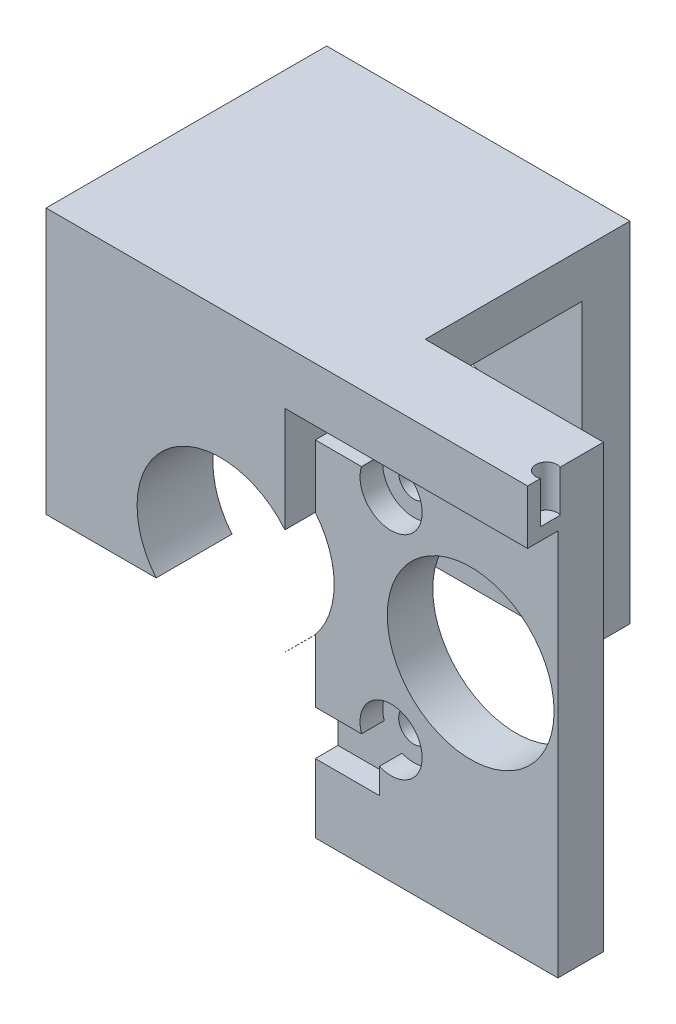
SolidWorks part; units mm, degrees
material "ABS"
ref_plane "Front Plane" through (0, 0, 0) normal (0, 0, 1) x (1, 0, 0)
ref_plane "Top Plane" through (0, 0, 0) normal (0, 1, 0) x (1, 0, 0)
ref_plane "Right Plane" through (0, 0, 0) normal (1, 0, 0) x (0, 0, -1)
sketch "Sketch1" plane through (0, 0, 0) normal (0, 0, 1) x (1, 0, 0)
  line L1 (-76.1871, 64.9281) -> (16.8129, 64.9281)
  line L2 (-76.1871, 64.9281) -> (-76.1871, -35.0719)
  line L3 (-76.1871, -35.0719) -> (16.8129, -35.0719)
  line L4 (16.8129, 64.9281) -> (16.8129, -35.0719)
  dimension "D1" = 93
  dimension "D2" = 100
extrude "Boss-Extrude2" add sketch "Sketch1" along normal blind 10 contours L1 L4 L3 L2
sketch "Sketch3" plane through (0, 0, 0) normal (0, 0, -1) x (-1, 0, 0)
  line L0 (76.1871, -35.0719) -> (-16.8129, -35.0719) construction
  line L1 (-16.8129, 64.9281) -> (-6.8129, 64.9281)
  line L2 (-16.8129, 64.9281) -> (-16.8129, -35.0719)
  line L3 (-16.8129, -35.0719) -> (-6.8129, -35.0719)
  line L4 (-6.8129, 64.9281) -> (-6.8129, -35.0719)
  line L5 (-16.8129, 64.9281) -> (-16.8129, -35.0719) construction
  dimension "D1" = 0
  dimension "D2" = 0
  dimension "D3" = 10
  dimension "D4" = 100
sketch "Sketch4" plane through (16.8129, 0, 0) normal (1, 0, 0) x (0, 0, -1)
  line L0 (-10, 64.9281) -> (-10, -35.0719) construction
  line L1 (-10, -5.0719) -> (0.01, -5.0719)
  line L2 (-10, -5.0719) -> (-10, -20.0719)
  line L3 (-10, -20.0719) -> (0.01, -20.0719)
  line L4 (0.01, -5.0719) -> (0.01, -20.0719)
  line L6 (-10, -35.0719) -> (0, -35.0719) construction
  dimension "D1" = 15
  dimension "D2" = 15
extrude "Boss-Extrude4" add sketch "Sketch4" along normal blind 24
sketch "Sketch5" plane through (0, -5.0719, 0) normal (0, 1, 0) x (1, 0, 0)
  line L0 (40.8129, -10) -> (16.8129, -10) construction
  line L2 (16.8129, 0) -> (16.8129, -10) construction
  circle A0 centre (26.8129, -5) radius 2
  dimension "D2" = 4
  dimension "D3" = 10
  dimension "D1" = 5
extrude "Cut-Extrude1" cut sketch "Sketch5" against normal blind 50
sketch "Sketch6" plane through (0, 0, 10) normal (0, 0, -1) x (-1, 0, 0)
  line L2 (76.1871, -35.0719) -> (-16.8129, -35.0719) construction
  line L3 (-16.8129, 64.9281) -> (-16.8129, -35.0719) construction
  circle A0 centre (-1.8129, -24.5719) radius 7.5
  dimension "D1" = 15
  dimension "D2" = 10.5
  dimension "D3" = 15
sketch "Sketch7" plane through (0, 0, 0) normal (0, 0, -1) x (-1, 0, 0)
  circle A0 centre (24.1871, 36.9281) radius 11
  circle A1 centre (24.1871, 36.9281) radius 9.3 construction
  dimension "D1" = 22
extrude "Cut-Extrude3" cut sketch "Sketch7" against normal blind 50
sketch "Sketch14" plane through (0, 0, 10) normal (0, 0, 1) x (1, 0, 0)
  line L0 (16.8129, 64.9281) -> (16.8129, -5.0719) construction
  line L1 (-44.6871, 15.7891) -> (16.8129, 15.7891)
  line L2 (-44.6871, 15.7891) -> (-44.6871, 57.7891)
  line L3 (-44.6871, 57.7891) -> (16.8129, 57.7891)
  line L4 (16.8129, 15.7891) -> (16.8129, 57.7891)
  dimension "D1" = 42
  dimension "D3" = 61.5
extrude "Cut-Extrude8" cut sketch "Sketch14" against normal blind 4
sketch "Sketch15" plane through (0, 0, 0) normal (0, 0, -1) x (-1, 0, 0)
  circle A0 centre (24.1871, 36.9281) radius 10
  circle A1 centre (24.1871, 36.9281) radius 11 construction
  dimension "D1" = 20
  dimension "D2" = 0
sketch "Sketch16" plane through (0, 0, 10) normal (0, 0, 1) x (1, 0, 0)
  line L0 (-43.6871, 56.9281) -> (14.3129, 56.9281) construction
  line L1 (-44.1871, 57.3281) -> (16.8129, 57.3281)
  line L2 (-44.1871, 57.3281) -> (-44.1871, 64.9281)
  line L3 (-44.1871, 64.9281) -> (16.8129, 64.9281)
  line L4 (16.8129, 57.3281) -> (16.8129, 64.9281)
  dimension "D1" = 0.4
sketch "Sketch17" plane through (0, 0, 10) normal (0, 0, 1) x (1, 0, 0)
  line L0 (16.8129, 15.7891) -> (16.8129, -5.0719) construction
  line L1 (-44.1871, 16.7281) -> (16.8129, 16.7281)
  line L2 (-44.1871, 16.7281) -> (-44.1871, -20.0719)
  line L3 (-44.1871, -20.0719) -> (16.8129, -20.0719)
  line L4 (16.8129, 16.7281) -> (16.8129, -20.0719)
  line L5 (-43.6871, 16.9281) -> (14.3129, 16.9281) construction
  line L6 (40.8129, -20.0719) -> (16.8129, -20.0719) construction
  line L9 (16.8129, -20.0719) -> (40.8129, -20.0719)
  line L10 (16.8129, -20.0719) -> (16.8129, -5.0719)
  line L11 (16.8129, -5.0719) -> (40.8129, -5.0719)
  line L12 (40.8129, -20.0719) -> (40.8129, -5.0719)
  line L13 (16.8129, -20.0719) -> (40.8129, -5.0719) construction
  line L14 (16.8129, -5.0719) -> (40.8129, -20.0719) construction
  point P16 (28.8129, -12.5719)
  dimension "D1" = 0.2
  dimension "D2" = 0
sketch "Sketch19" plane through (0, 0, 0) normal (0, 0, -1) x (-1, 0, 0)
  line L1 (-16.8129, 64.9281) -> (-16.8129, -35.0719) construction
  circle A0 centre (53.1871, 36.9281) radius 11
  circle A1 centre (24.1871, 36.9281) radius 10 construction
  dimension "D1" = 22
  dimension "D3" = 0
  dimension "D2" = 70
extrude "Cut-Extrude11" cut sketch "Sketch19" against normal blind 15
sketch "Sketch20" plane through (0, 0, 6) normal (0, 0, 1) x (1, 0, 0)
  circle A0 centre (-34.6871, 50.9281) radius 2
  circle A1 centre (5.3129, 50.9281) radius 2
  circle A2 centre (-34.6871, 22.9281) radius 2
  circle A3 centre (5.3129, 22.9281) radius 2
  arc A5 (-27.0471, 34.1316) -> (-27.0471, 39.7246) centre (-24.1871, 36.9281) ccw construction
  circle A6 centre (-24.1871, 36.9281) radius 11 construction
  dimension "D1" = 4
  dimension "D2" = 4
  dimension "D3" = 4
  dimension "D4" = 4
  dimension "D5" = 0
  dimension "D6" = 28
  dimension "D7" = 0
  dimension "D8" = 40
  dimension "D9" = 14
  dimension "D10" = 10.5
  dimension "D11" = 28
  dimension "D12" = 40
extrude "Cut-Extrude12" cut sketch "Sketch20" against normal blind 10
sketch "Sketch8" plane through (0, 64.9281, 0) normal (0, 1, 0) x (1, 0, 0)
  line L0 (-76.1871, -10) -> (16.8129, -10) construction
  line L5 (16.8129, 0) -> (12.3014, -10) construction
  line L6 (16.8129, -10) -> (7.8859, 0) construction
  line L8 (16.8129, -10) -> (16.8129, 0) construction
  line L9 (-76.1871, 0) -> (16.8129, 0) construction
  circle A0 centre (11.8129, -7) radius 1.4
  circle A1 centre (-13.1871, -7) radius 1.4
  point P4 (13.816, -6.6429)
  dimension "D1" = 25
  dimension "D2" = 5
  dimension "D3" = 2.8
  dimension "D4" = 7
  dimension "D5" = 7
extrude "Cut-Extrude4" cut sketch "Sketch8" against normal blind 5.5 contours A1 | A0 region at (-13.1871, 64.9281, 7)
sketch "Sketch21" plane through (0, 0, 0) normal (0, 0, -1) x (-1, 0, 0)
  line L1 (76.1871, 64.9281) -> (36.1871, 64.9281)
  line L2 (76.1871, 64.9281) -> (76.1871, 58.9281)
  line L3 (76.1871, 58.9281) -> (36.1871, 58.9281)
  line L4 (36.1871, 64.9281) -> (36.1871, 58.9281)
  dimension "D1" = 6
  dimension "D2" = 40
extrude "Boss-Extrude5" add sketch "Sketch21" along normal blind 27
sketch "Sketch22" plane through (0, 58.9281, 0) normal (0, -1, 0) x (1, 0, 0)
  line L0 (-76.1871, -27) -> (-76.1871, 0) construction
  line L1 (-36.1871, -27) -> (-76.1871, -27)
  line L2 (-36.1871, -27) -> (-36.1871, -20.7)
  line L3 (-36.1871, -20.7) -> (-76.1871, -20.7)
  line L4 (-76.1871, -27) -> (-76.1871, -20.7)
  dimension "D1" = 6.3
extrude "Boss-Extrude7" add sketch "Sketch22" along normal blind 40
sketch "Sketch23" plane through (0, 0, 10) normal (0, 0, 1) x (1, 0, 0)
  circle A0 centre (-53.1871, 36.9281) radius 8
  arc A1 (-44.6871, 43.9102) -> (-44.6871, 29.9459) centre (-53.1871, 36.9281) ccw construction
  dimension "D1" = 16
  dimension "D2" = 0
extrude "Cut-Extrude13" cut sketch "Sketch23" against normal blind 40
sketch "Sketch24" plane through (0, 0, 10) normal (0, 0, 1) x (1, 0, 0)
  line L1 (-76.1871, -35.0719) -> (42.0908, -35.0719)
  line L2 (-76.1871, -35.0719) -> (-76.1871, 6.7281)
  line L3 (-76.1871, 6.7281) -> (42.0908, 6.7281)
  line L4 (42.0908, -35.0719) -> (42.0908, 6.7281)
  dimension "D1" = 41.8
extrude "Cut-Extrude14" cut sketch "Sketch24" against normal blind 40
sketch "Sketch25" plane through (0, 0, 10) normal (0, 0, 1) x (1, 0, 0)
  line L5 (-44.6871, 29.9459) -> (-44.6871, 15.7891) construction
  line L6 (-76.1871, 6.7281) -> (-44.6871, 6.7281)
  line L7 (-76.1871, 6.7281) -> (-76.1871, 29.9281)
  line L8 (-76.1871, 29.9281) -> (-44.6871, 29.9281)
  line L9 (-44.6871, 6.7281) -> (-44.6871, 29.9281)
  arc A2 (-44.6871, 43.9102) -> (-44.6871, 29.9459) centre (-53.1871, 36.9281) ccw construction
  dimension "D1" = 7
extrude "Cut-Extrude15" cut sketch "Sketch25" against normal blind 20
sketch "Sketch26" plane through (0, 0, 6) normal (0, 0, 1) x (1, 0, 0)
  line L1 (-44.6871, 15.7891) -> (-36.2375, 15.7891)
  line L2 (-44.6871, 15.7891) -> (-44.6871, 21.6647)
  line L3 (-44.6871, 21.6647) -> (-36.2375, 21.6647)
  line L4 (-36.2375, 15.7891) -> (-36.2375, 21.6647)
  line L5 (-44.6871, 57.7891) -> (-36.2375, 57.7891)
  line L6 (-44.6871, 57.7891) -> (-44.6871, 52.1914)
  line L7 (-44.6871, 52.1914) -> (-36.2375, 52.1914)
  line L8 (-36.2375, 57.7891) -> (-36.2375, 52.1914)
  line L9 (6.8634, 52.1914) -> (14.3021, 52.1914)
  line L10 (6.8634, 52.1914) -> (6.8634, 57.7891)
  line L11 (6.8634, 57.7891) -> (14.3021, 57.7891)
  line L12 (14.3021, 52.1914) -> (14.3021, 57.7891)
  line L13 (6.8634, 20.9281) -> (14.3021, 20.9281)
  line L14 (6.8634, 20.9281) -> (6.8634, 15.7891)
  line L15 (6.8634, 15.7891) -> (14.3021, 15.7891)
  line L16 (14.3021, 20.9281) -> (14.3021, 15.7891)
  circle A0 centre (-34.6871, 22.9281) radius 2 construction
  circle A1 centre (-34.6871, 50.9281) radius 2 construction
  circle A2 centre (5.3129, 50.9281) radius 2 construction
  circle A3 centre (5.3129, 22.9281) radius 4
  circle A4 centre (5.3129, 50.9281) radius 4
  circle A5 centre (-34.6871, 50.9281) radius 4
  circle A6 centre (-34.6871, 22.9281) radius 4
  circle A7 centre (5.3129, 50.9281) radius 4
  circle A8 centre (5.3129, 22.9281) radius 4
  circle A9 centre (-34.6871, 50.9281) radius 4
  circle A10 centre (-34.6871, 22.9281) radius 4
  line M5 (-44.6871, 57.7891) -> (-44.6871, 43.9102)
  line M8 (-44.6871, 29.9281) -> (-44.6871, 15.7891)
  line M9 (-44.6871, 15.7891) -> (16.8129, 15.7891)
  line M11 (16.8129, 57.7891) -> (-44.6871, 57.7891)
  dimension "D1" = 8
  dimension "D2" = 8
  dimension "D3" = 8
  dimension "D4" = 8
extrude "Cut-Extrude18" cut sketch "Sketch26" against normal blind 3 contours A4 L9 L12 L10 M11 | A3 L14 L16 L13 M9 | A5 L8 L7 M11 M5 | A6 L3 L4 M8 M9 region at (-40.7189, 18.5733, 6) region at (10.7466, 18.2528, 6) region at (10.8466, 55.1634, 6) region at (-40.7326, 55.141, 6)
sketch "Sketch27" plane through (0, 0, 6) normal (0, 0, 1) x (1, 0, 0)
  circle A0 centre (5.3129, 50.9281) radius 4.1
  circle A1 centre (5.3129, 22.9281) radius 4
  circle A2 centre (-34.6871, 50.9281) radius 4.1
  circle A3 centre (-34.6871, 22.9281) radius 4.1
  dimension "D1" = 8.2
  dimension "D2" = 8.2
  dimension "D3" = 8
  dimension "D4" = 8.2
extrude "Cut-Extrude29" cut sketch "Sketch27" against normal blind 3
sketch "Sketch28" plane through (0, 0, 0) normal (0, 0, -1) x (-1, 0, 0)
  line L5 (-16.8129, 6.7281) -> (44.6871, 6.7281) construction
  line L6 (-16.8129, 64.9281) -> (12.6871, 64.9281)
  line L7 (-16.8129, 64.9281) -> (-16.8129, 6.7281)
  line L8 (-16.8129, 6.7281) -> (12.6871, 6.7281)
  line L9 (12.6871, 64.9281) -> (12.6871, 6.7281)
  circle A1 centre (34.6871, 22.9281) radius 2 construction
  dimension "D1" = 22
extrude "Cut-Extrude30" cut sketch "Sketch28" against normal blind 23
sketch "Sketch29" plane through (0, 15.7891, 0) normal (0, 1, 0) x (1, 0, 0)
  line L1 (-44.6871, -10) -> (-12.6871, -10)
  line L2 (-44.6871, -10) -> (-44.6871, -6)
  line L3 (-44.6871, -6) -> (-12.6871, -6)
  line L4 (-12.6871, -10) -> (-12.6871, -6)
extrude "Cut-Extrude31" cut sketch "Sketch29" against normal blind 23
